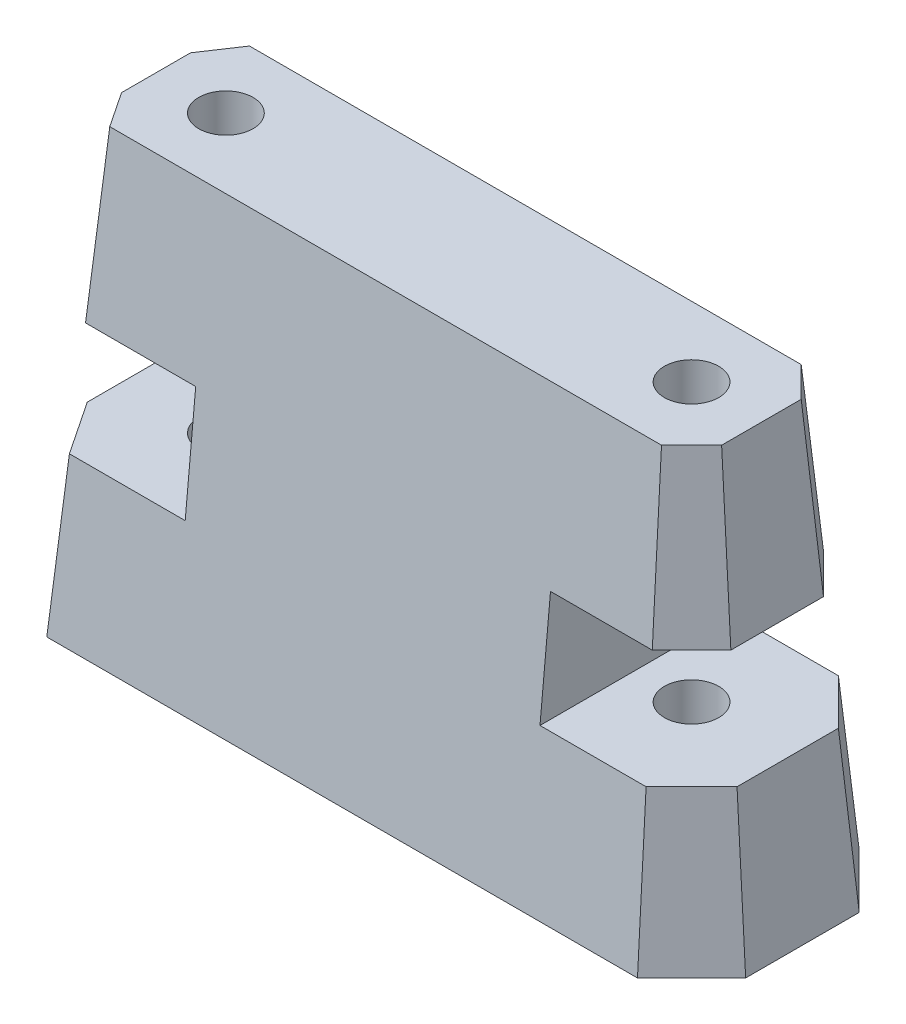
SolidWorks part; units mm, degrees
ref_plane "Front Plane" through (0, 0, 0) normal (0, 0, 1) x (1, 0, 0)
ref_plane "Top Plane" through (0, 0, 0) normal (0, 1, 0) x (1, 0, 0)
ref_plane "Right Plane" through (0, 0, 0) normal (1, 0, 0) x (0, 0, -1)
sketch "Sketch1" plane through (0, 0, 0) normal (0, 1, 0) x (1, 0, 0)
  line L0 (-25.1745, 6.3) -> (-27.3, 3.111)
  line L1 (-27.3, 3.111) -> (-27.3, -3.111)
  line L2 (-27.3, -3.111) -> (-25.1745, -6.3)
  line L3 (-25.1745, -6.3) -> (-13.6955, -6.3)
  line L5 (-13.6955, 6.3) -> (-25.1745, 6.3)
  line L6 (24.5887, 6.3) -> (13.6955, 6.3)
  line L8 (13.6955, -6.3) -> (24.5887, -6.3)
  line L9 (24.5887, -6.3) -> (27.3, -3.5887)
  line L10 (27.3, -3.5887) -> (27.3, 3.5887)
  line L11 (27.3, 3.5887) -> (24.5887, 6.3)
  line L12 (-13.6955, 6.3) -> (13.6955, 6.3)
  line L13 (13.6955, -6.3) -> (-13.6955, -6.3)
  arc A0 (21, 2.45) -> (21, -2.45) centre (21, 0) ccw
  arc A1 (21, -2.45) -> (21, 2.45) centre (21, 0) ccw
  arc A2 (-21, -2.45) -> (-21, 2.45) centre (-21, 0) ccw
  arc A3 (-21, 2.45) -> (-21, -2.45) centre (-21, 0) ccw
  dimension "D1" = 2.45
  dimension "D2" = 13.6955
  dimension "D3" = 21
  dimension "D4" = 24.5887
  dimension "D5" = 27.3
  dimension "D6" = 13.6955
  dimension "D7" = 21
  dimension "D8" = 25.1745
  dimension "D9" = 27.3
  dimension "D10" = 3.111
  dimension "D11" = 3.5887
  dimension "D12" = 3.111
ref_plane "Plane1" through (0, -39, 0) normal (0, 1, 0) x (1, 0, 0)
sketch "Sketch2" plane through (0, -39, 0) normal (0, 1, 0) x (1, 0, 0)
  line L0 (24.5887, 6.3) -> (13.6955, 6.3) construction
  line L5 (27.3, 3.5887) -> (24.5887, 6.3) construction
  line L6 (27.3, -3.5887) -> (27.3, 3.5887) construction
  line L7 (24.5887, -6.3) -> (27.3, -3.5887) construction
  line L8 (13.6955, -6.3) -> (24.5887, -6.3) construction
  line L9 (13.6955, -6.3) -> (-13.6955, -6.3) construction
  line L10 (-25.1745, -6.3) -> (-13.6955, -6.3) construction
  line L11 (-27.3, -3.111) -> (-25.1745, -6.3) construction
  line L12 (-27.3, 3.111) -> (-27.3, -3.111) construction
  line L13 (-25.1745, 6.3) -> (-27.3, 3.111) construction
  line L14 (-13.6955, 6.3) -> (-25.1745, 6.3) construction
  line L15 (-13.6955, 6.3) -> (13.6955, 6.3) construction
  line L16 (24.5887, 6.3) -> (13.6955, 6.3)
  line L17 (27.3, 3.5887) -> (24.5887, 6.3)
  line L18 (27.3, -3.5887) -> (27.3, 3.5887)
  line L19 (24.5887, -6.3) -> (27.3, -3.5887)
  line L20 (13.6955, -6.3) -> (24.5887, -6.3)
  line L21 (13.6955, -6.3) -> (-13.6955, -6.3)
  line L22 (-25.1745, -6.3) -> (-13.6955, -6.3)
  line L23 (-27.3, -3.111) -> (-25.1745, -6.3)
  line L24 (-27.3, 3.111) -> (-27.3, -3.111)
  line L25 (-25.1745, 6.3) -> (-27.3, 3.111)
  line L26 (-13.6955, 6.3) -> (-25.1745, 6.3)
  line L27 (-13.6955, 6.3) -> (13.6955, 6.3)
  line L28 (26.1213, 10) -> (13.6955, 10)
  line L29 (-13.6955, 10) -> (13.6955, 10)
  line L30 (-13.6955, 10) -> (-27.1549, 10)
  line L31 (-27.1549, 10) -> (-31, 4.2311)
  line L32 (-31, 4.2311) -> (-31, -4.2311)
  line L33 (-31, -4.2311) -> (-27.1549, -10)
  line L34 (-27.1549, -10) -> (-13.6955, -10)
  line L35 (13.6955, -10) -> (-13.6955, -10)
  line L36 (13.6955, -10) -> (26.1213, -10)
  line L37 (26.1213, -10) -> (31, -5.1213)
  line L38 (31, -5.1213) -> (31, 5.1213)
  line L39 (31, 5.1213) -> (26.1213, 10)
  point P0 (-27.3, 3.111)
  dimension "D1" = 20
loft "Loft1" add section "Sketch1" section "Sketch2" connector at (-25.1745, 0, 6.3) connector at (-27.1549, -39, 10)
extrude "Cut-Extrude1" cut sketch "Sketch1<4>" against normal through all contours A3 A2 | A0 A1
sketch "Sketch1<4>" plane through (0, 0, 0) normal (0, 1, 0) x (1, 0, 0) same geometry as "Sketch1"
sketch "Sketch3" plane through (0, 0, 0) normal (0, 0, 1) x (1, 0, 0)
  line L0 (-25.1745, 0) -> (-13.6955, 0) construction
  line L1 (-16, -15) -> (-36.915, -15)
  line L2 (-16, -15) -> (-16, -25)
  line L3 (-16, -25) -> (-36.915, -25)
  line L4 (-36.915, -15) -> (-36.915, -25)
  line L5 (-27.1549, -39) -> (-13.6955, -39) construction
  point P4 (-16, -20.4854)
  dimension "D1" = 5
  dimension "D2" = 10
  dimension "D3" = 15
  dimension "D4" = 14
extrude "Cut-Extrude2" cut sketch "Sketch3" against normal through all both and the other way through all
mirror "Mirror1" about plane through (0, 0, 0) normal (1, 0, 0) of "Cut-Extrude2"
